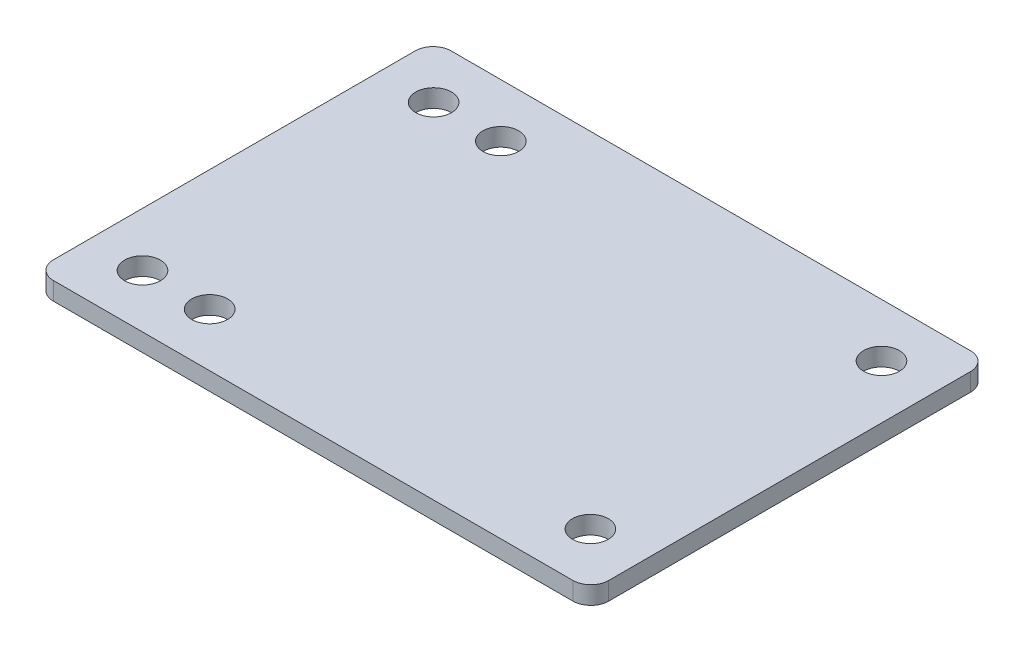
SolidWorks part; units mm, degrees
ref_plane "Front Plane" through (0, 0, 0) normal (0, 0, 1) x (1, 0, 0)
ref_plane "Top Plane" through (0, 0, 0) normal (0, 1, 0) x (1, 0, 0)
ref_plane "Right Plane" through (0, 0, 0) normal (1, 0, 0) x (0, 0, -1)
sketch "Sketch1" plane through (0, 0, 0) normal (0, 1, 0) x (1, 0, 0)
  line L1 (-39.37, -28.194) -> (39.37, -28.194)
  line L2 (-39.37, -28.194) -> (-39.37, 28.194)
  line L3 (-39.37, 28.194) -> (39.37, 28.194)
  line L4 (39.37, -28.194) -> (39.37, 28.194)
  line L5 (-39.37, -28.194) -> (39.37, 28.194) construction
  line L6 (-39.37, 28.194) -> (39.37, -28.194) construction
  point P0 (0, 0)
  dimension "D1" = 78.74
  dimension "D2" = 56.388
extrude "Boss-Extrude1" add sketch "Sketch1" along normal blind 2.54
fillet "Fillet1" radius 2.54 4 edges at (39.37, 1.27, -28.194) (39.37, 1.27, 28.194) (-39.37, 1.27, -28.194) (-39.37, 1.27, 28.194)
sketch "Sketch2" plane through (0, 2.54, 0) normal (0, 1, 0) x (1, 0, 0)
  line L1 (31.75, -20.6375) -> (-31.75, -20.6375)
  line L2 (31.75, -20.6375) -> (31.75, 20.6375)
  line L3 (31.75, 20.6375) -> (-31.75, 20.6375)
  line L4 (-31.75, -20.6375) -> (-31.75, 20.6375)
  line L5 (31.75, -20.6375) -> (-31.75, 20.6375) construction
  line L6 (31.75, 20.6375) -> (-31.75, -20.6375) construction
  circle A0 centre (31.75, 20.6375) radius 2.54
  circle A1 centre (31.75, -20.6375) radius 2.54
  circle A2 centre (-31.75, -20.6375) radius 2.54
  circle A3 centre (-31.75, 20.6375) radius 2.54
  circle A4 centre (-22.225, -20.6375) radius 2.54
  circle A5 centre (-22.225, 20.6375) radius 2.54
  point P0 (0, 0)
  point P9 (29.9546, -20.6375)
  point P11 (-31.75, -23.0104)
  point P13 (-31.75, 18.7712)
  point P15 (-23.0645, -20.6375)
  point P18 (-23.0645, 20.6375)
  dimension "D3" = 53.975
  dimension "D4" = 53.975
  dimension "D1" = 63.5
  dimension "D2" = 41.275
extrude "Cut-Extrude1" cut sketch "Sketch2" against normal blind 2.54 contours A2 | A4 | A3 | A5 | A1 | A0
